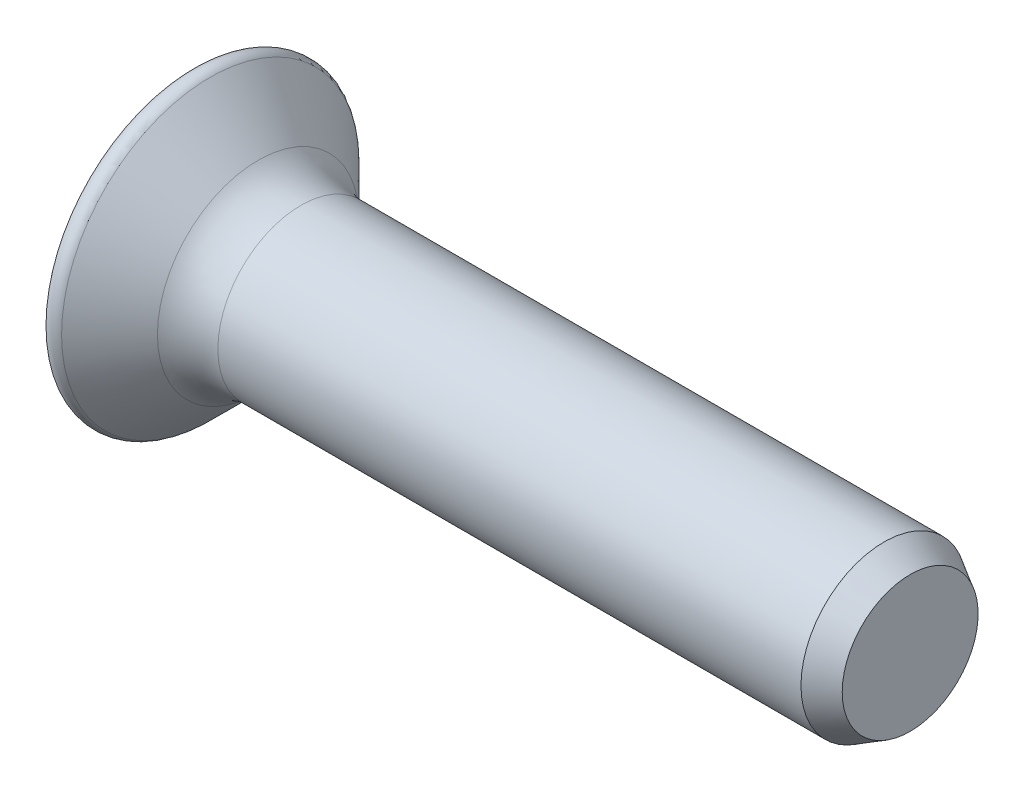
SolidWorks part; units mm, degrees
ref_plane "Front Plane" through (0, 0, 0) normal (0, 0, 1) x (1, 0, 0)
ref_plane "Top Plane" through (0, 0, 0) normal (0, 1, 0) x (1, 0, 0)
ref_plane "Right Plane" through (0, 0, 0) normal (1, 0, 0) x (0, 0, -1)
sketch "Sketch1" plane through (0, 0, 0) normal (0, 0, 1) x (1, 0, 0)
  line L0 (0, 0) -> (6.2784, 0) construction
  line L3 (-1.6, 0) -> (-1.6, -1.8061) construction
  line L4 (-1.6, 0) -> (8.4, 0)
  line L5 (0, 1.1) -> (8.4, 1.1)
  line L6 (8.4, 1.1) -> (8.4, 0)
  line L7 (0, 1.1) -> (-0.869, 1.969)
  arc A0 (-1.1, 1.9365) -> (-1.6, 0) centre (2.4, 0) ccw
  arc A1 (-1.1, 1.9365) -> (-0.869, 1.969) centre (-0.9723, 1.8658) cw
  dimension "D1" = 45
  dimension "l" = 9.5
revolve "Revolve1" add sketch "Sketch1" angle 360 about L0
cosmetic thread "ThreadCosmetic" [suppressed] parameters "D1"=9.3, "D2"=1.65
chamfer "Chamfer1" distance 0.2 angle 60 1 edges at (8.4, 0, 1.1) first distance on face at (8.4, 0, 1.1)
sketch "Sketch5" plane through (0, 0, 0) normal (0, 0, 1) x (1, 0, 0)
  line L0 (0.3703, 0.825) -> (0.2069, 0.825)
  line L1 (0.2069, 0.825) -> (0.0481, 1.1)
  line L2 (0.3703, 0.825) -> (0.529, 1.1)
  line L3 (0.0481, 1.1) -> (0.0481, 1.35)
  line L4 (0.529, 1.1) -> (0.529, 1.35)
  line L5 (0.0481, 1.35) -> (0.529, 1.35)
  line L6 (0.2886, 0.825) -> (0.2886, 0) construction
  line L7 (0, 0) -> (7.3035, 0) construction
  line L9 (0, 1.1) -> (0, -1.1) construction
  line L12 (8.0536, 1.1) -> (0, 1.1) construction
  dimension "D2" = 60
  dimension "D3" = 0.25
  dimension "minordia" = 1.65
  dimension "threadstart" = 0.2886
revolve "ThreadSchematic" [suppressed] cut sketch "Sketch5" angle 360 about L7
pattern_linear "ThdSchPat" [suppressed] count 18 spacing 0.4809 along (1, 0, 0) of bodies 105
sketch "Sketch2" plane through (0, 0, 0) normal (0, 0, 1) x (1, 0, 0)
  line L0 (0, 0) -> (5.7679, 0) construction
  line L1 (8.4, 0) -> (6.4947, 1.1)
  line L2 (8.4, 1.1) -> (8.4, 0) construction
  line L4 (6.4947, 1.1) -> (6.4947, 1.2)
  line L5 (6.4947, 1.2) -> (8.5, 1.2)
  line L6 (8.5, 1.2) -> (8.5, 0)
  line L7 (8.5, 0) -> (8.4, 0)
  point P5 (0, 1.1)
  dimension "D1" = 30
  dimension "D2" = 0.1
  dimension "D3" = 0.1
revolve "EndCone" [suppressed] cut sketch "Sketch2" angle 360 about L0
ref_plane "Plane4" through (-1.6, 0, 0) normal (1, 0, 0) x (0, 0, -1)
sketch "Sketch3" plane through (-1.6, 0, 0) normal (1, 0, 0) x (0, 0, -1)
  line L0 (0, 2.343) -> (0, -2.4842) construction
  line L1 (2.7661, 0) -> (-3.4558, 0) construction
  line L2 (-0.22, 1.1) -> (0.22, 1.1)
  line L3 (0.22, 1.1) -> (0.1467, 0.7333)
  line L4 (0, 0) -> (1.9578, 1.9578) construction
  line L5 (0.1467, 0.7333) -> (0.3614, 0.3614)
  line L6 (0.1467, 0.7333) -> (0, 0) construction
  line L7 (-0.1467, 0.7333) -> (-0.3614, 0.3614)
  line L8 (-0.22, 1.1) -> (-0.1467, 0.7333)
  line L9 (1.1, 0.22) -> (1.1, -0.22)
  line L10 (1.1, -0.22) -> (0.7333, -0.1467)
  line L11 (0.7333, -0.1467) -> (0.3614, -0.3614)
  line L12 (0.7333, 0.1467) -> (0.3614, 0.3614)
  line L13 (1.1, 0.22) -> (0.7333, 0.1467)
  line L14 (0.22, -1.1) -> (-0.22, -1.1)
  line L15 (-0.22, -1.1) -> (-0.1467, -0.7333)
  line L16 (-0.1467, -0.7333) -> (-0.3614, -0.3614)
  line L17 (0.1467, -0.7333) -> (0.3614, -0.3614)
  line L18 (0.22, -1.1) -> (0.1467, -0.7333)
  line L19 (-1.1, -0.22) -> (-1.1, 0.22)
  line L20 (-1.1, 0.22) -> (-0.7333, 0.1467)
  line L21 (-0.7333, 0.1467) -> (-0.3614, 0.3614)
  line L22 (-0.7333, -0.1467) -> (-0.3614, -0.3614)
  line L23 (-1.1, -0.22) -> (-0.7333, -0.1467)
  point P14 (0, 1.1)
  point P23 (1.1, 0)
  point P30 (0, -1.1)
  point P37 (-1.1, 0)
  dimension "D1" = 45
  dimension "D3" = 0.44
  dimension "D4" = 75
  dimension "D5" = 1.4667
  dimension "m" = 2.2
extrude "Cut-Extrude1" cut sketch "Sketch3" along normal blind 0.8 draft 6
sketch "Sketch4" plane through (-1.6, 0, 0) normal (1, 0, 0) x (0, 0, -1)
  line L0 (0, 2.1951) -> (0, -2.1951) construction
  line L1 (2.1996, 0) -> (-2.3835, 0) construction
  line L2 (-0.9723, -0.9723) -> (0.9723, 0.9723) construction
  line L3 (1.1, 0.275) -> (-1.1, 0.275)
  line L4 (1.1, 0.275) -> (1.1, -0.275)
  line L5 (1.1, -0.275) -> (-1.1, -0.275)
  line L6 (-1.1, 0.275) -> (-1.1, -0.275)
  line L7 (0.275, 1.1) -> (-0.275, 1.1)
  line L8 (0.275, 1.1) -> (0.275, -1.1)
  line L9 (0.275, -1.1) -> (-0.275, -1.1)
  line L10 (-0.275, 1.1) -> (-0.275, -1.1)
  line L11 (0.9723, 0.9723) -> (0.4468, 0.275)
  line L12 (0.9723, 0.9723) -> (0.275, 0.4468)
  line L13 (0.275, 0.4468) -> (-0.275, 0.4468) construction
  line L14 (0, 0) -> (-0.9723, 0.9723) construction
  line L15 (-0.9723, -0.9723) -> (-0.275, -0.4468)
  line L16 (-0.9723, -0.9723) -> (-0.4468, -0.275)
  line L17 (-0.275, 0.4468) -> (-0.9723, 0.9723)
  line L18 (-0.9723, 0.9723) -> (-0.4468, 0.275)
  line L19 (-0.4468, -0.275) -> (-0.4468, 0.275) construction
  line L20 (0.4468, -0.275) -> (0.9723, -0.9723)
  line L21 (0.9723, -0.9723) -> (0.275, -0.4468)
  circle A0 centre (0, 0) radius 1.375 construction
  dimension "D1" = 2.75
  dimension "D2" = 0.55
  dimension "m" = 2.2
  dimension "D3" = 45
  dimension "D4" = 8
  dimension "D5" = 45
extrude "TypeZ" [suppressed] cut sketch "Sketch4" along normal blind 0.8
fillet "Fillet1" radius 0.8 1 edges at (0, 0, 1.1)
equation "\"D1@ThreadCosmetic\" = \"l@Sketch1\" - \"D1@Chamfer1\""
equation "\"minordia@Sketch5\" = \"D2@ThreadCosmetic\""
equation "\"D1@Plane4\" = \"k@Sketch1\" + \"f@Sketch1\""
equation "\"D5@Sketch3\" = \"m@Sketch3\" * 2 / 3"
equation "\"D3@Sketch3\" = \"m@Sketch3\" / 5"
equation "\"D1@Cut-Extrude1\" =  ( \"k@Sketch1\" + \"f@Sketch1\" )  / 2"
equation "\"m@Sketch4\" = \"m@Sketch3\""
equation "\"D2@Sketch4\" =  \"m@Sketch4\" / 4"
equation "\"D1@TypeZ\" =  ( \"k@Sketch1\" + \"f@Sketch1\" )  / 2"
equation "\"D1@Sketch4\" = \"m@Sketch4\" * 5 / 4"
equation "\"threadstart@Sketch5\" = \"advance@Sketch5\"*0.6"
equation "\"D1@ThdSchPat\" = int(((\"l@Sketch1\"-\"k@Sketch1\")/\"advance@Sketch5\") + 0.8)"
equation "\"D3@ThdSchPat\" = \"advance@Sketch5\""
